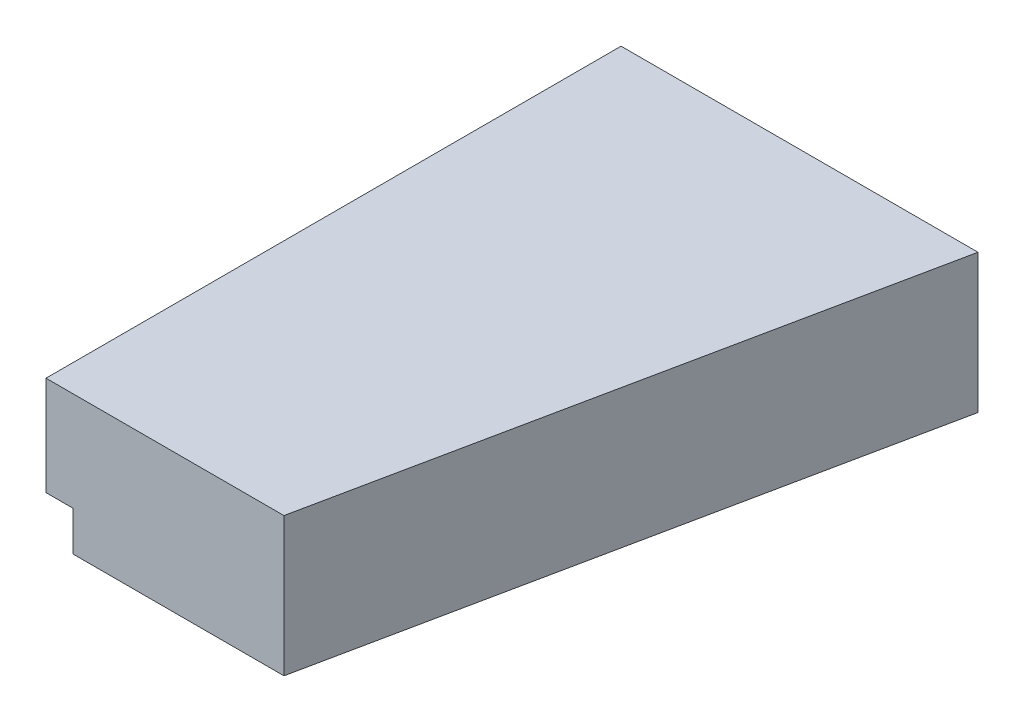
SolidWorks part; units mm, degrees
ref_plane "Front Plane" through (0, 0, 0) normal (1, 0, 0) x (0, 1, 0)
ref_plane "Top Plane" through (0, 0, 0) normal (0, 0, 1) x (0, 1, 0)
ref_plane "Right Plane" through (0, 0, 0) normal (0, 1, 0) x (-1, 0, 0)
sketch "Sketch1" plane through (0, 0, 0) normal (0, 1, 0) x (-1, 0, 0)
  line L0 (-13.4363, 2.5951) -> (16.5637, 147.5951)
  line L1 (-13.4363, -4.9049) -> (-8.4363, -4.9049)
  line L2 (-13.4363, -4.9049) -> (-13.4363, 2.5951)
  line L3 (-13.4363, 2.5951) -> (-8.4363, 2.5951)
  line L4 (-8.4363, -4.9049) -> (-8.4363, 2.5951)
  line L13 (-13.4363, 2.5951) -> (16.5637, 147.5951)
  line L14 (-13.4363, 2.5951) -> (-3.6437, 0.569)
  line L15 (-13.4363, 2.5951) -> (66.5637, 2.5951) construction
  line L16 (-13.4363, 2.5951) -> (-13.4363, 137.5951) construction
  line L17 (-13.4363, 137.5951) -> (66.5637, 137.5951) construction
  line L18 (66.5637, 2.5951) -> (66.5637, 137.5951) construction
  line L19 (66.5637, 137.5951) -> (16.5637, 137.5951)
  line L20 (66.5637, 137.5951) -> (66.5637, 147.5951)
  line L21 (66.5637, 147.5951) -> (16.5637, 147.5951)
  line L22 (16.5637, 137.5951) -> (16.5637, 147.5951)
  line L23 (16.5637, 147.5951) -> (26.3563, 145.569)
  line L24 (-3.6437, 0.569) -> (26.3563, 145.569)
  line L25 (-8.4363, 2.5951) -> (-3.2246, 2.5951)
  line L27 (-3.2246, 2.5951) -> (66.5637, 2.5951)
  line L28 (-3.2246, 2.5951) -> (-3.2246, 7.5951)
  line L29 (-3.2246, 7.5951) -> (66.5637, 7.5951)
  line L30 (66.5637, 2.5951) -> (66.5637, 7.5951)
  line L35 (66.5637, 147.5951) -> (76.5637, 147.5951)
  line L36 (66.5637, 147.5951) -> (66.5637, 2.5951)
  line L37 (66.5637, 2.5951) -> (76.5637, 2.5951)
  line L38 (76.5637, 147.5951) -> (76.5637, 2.5951)
  dimension "D1" = 7.5
  dimension "D3" = 135
  dimension "D4" = 80
  dimension "D5" = 10
  dimension "D7" = 10
  dimension "D9" = 5
  dimension "D8" = 10
  dimension "D6" = 50
extrude "Boss-Extrude1" add sketch "Sketch1" along normal blind 35 contours L24 L19 L20 L21 L23 | L19 L24 L23 L22 | L3 L25 L24 L19 L22 L0 | L29 L28 L24 | L27 L30 L29 L24 | L38 L35 L20 L36 L30 L37 region at (-5.7274, 0, 70.7433) region at (-20.91, 0, 142.2574) region at (-45.5816, 0, 142.6608) region at (-71.5637, 0, 75.0951) region at (2.8797, 0, 5.9284) region at (-31.9275, 0, 5.0889)
sketch "Sketch2" plane through (0, 35, 0) normal (0, 1, 0) x (-1, 0, 0)
  line L0 (16.5637, 147.5951) -> (76.5637, 147.5951)
  line L1 (76.5637, 147.5951) -> (76.5637, 2.5951)
  line L2 (76.5637, 2.5951) -> (-13.4363, 2.5951)
  line L3 (-13.4363, 2.5951) -> (16.5637, 147.5951)
  line L5 (-13.4363, 2.5951) -> (76.5637, 2.5951) construction
extrude "Boss-Extrude2" add sketch "Sketch2" against normal blind 10
sketch "Sketch3" plane through (0, 0, 0) normal (0, -1, 0) x (1, 0, 0)
  line L1 (-24.7065, 147.5951) -> (-66.5637, 147.5951)
  line L2 (-24.7065, 147.5951) -> (-24.7065, 137.5951)
  line L3 (-24.7065, 137.5951) -> (-66.5637, 137.5951)
  line L4 (-66.5637, 147.5951) -> (-66.5637, 137.5951)
  line L8 (13.4363, 2.5951) -> (-76.5637, 2.5951) construction
  line L17 (-76.5637, 147.5951) -> (-16.5637, 147.5951) construction
  line L19 (-24.7065, 137.5951) -> (2.1901, 7.5951) construction
  line L22 (3.2246, 2.5951) -> (-24.7065, 137.5951)
  line L23 (3.2246, 2.5951) -> (13.0172, 4.6211)
  line L24 (-24.7065, 137.5951) -> (-14.9139, 139.6211)
  line L26 (13.0172, 4.6211) -> (-14.9139, 139.6211)
  line L28 (-27.9565, 140.8451) -> (-63.3137, 140.8451)
  line L29 (-63.3137, 144.3451) -> (-63.3137, 140.8451)
  line L30 (-27.9565, 144.3451) -> (-63.3137, 144.3451)
  line L31 (-27.9565, 144.3451) -> (-27.9565, 140.8451)
  line L32 (-20.8654, 135.071) -> (-17.438, 135.7801)
  line L33 (9.1761, 7.1453) -> (-17.438, 135.7801)
  line L34 (5.7487, 6.4361) -> (9.1761, 7.1453)
  line L35 (5.7487, 6.4361) -> (-20.8654, 135.071)
  line L36 (-17.438, 135.7801) -> (-20.8654, 135.071)
  line L37 (-20.8654, 135.071) -> (-23.4566, 147.5951)
  line L38 (-17.438, 135.7801) -> (-19.8825, 147.5951)
  line L39 (-27.9565, 140.8451) -> (-18.4859, 140.8451)
  line L40 (-27.9565, 144.3451) -> (-19.2101, 144.3451)
  line L41 (-19.2101, 144.3451) -> (-18.4859, 140.8451)
  point P5 (-4.1009, 2.5951)
  dimension "D1" = 3.25
extrude "Cut-Extrude1" cut sketch "Sketch3" against normal blind 10 contours L31 L30 L29 L28 | L35 L34 L33 L32 region at (-45.6351, 0, 142.5951) region at (-5.8447, 0, 71.1081)
sketch "Sketch4" plane through (0, 0, 22.5951) normal (0, 1, 0) x (1, 0, 0)
  line L5 (13.4363, 20) -> (-76.5637, 20) construction
  line L6 (-66.5637, 15) -> (2.1901, 15)
  line L7 (-66.5637, 15) -> (-66.5637, 20)
  line L8 (-66.5637, 20) -> (2.1901, 20)
  line L9 (2.1901, 15) -> (2.1901, 20)
  line L10 (2.1901, 15) -> (3.2246, 20)
  line L11 (2.1901, 15) -> (-24.7065, -115) construction
  line L12 (3.2246, 20) -> (2.1901, 20)
  line M13 (2.1901, 15) -> (-66.5637, 15)
  line M20 (-76.5637, 20) -> (13.4363, 20)
extrude "Cut-Extrude2" cut sketch "Sketch4" along normal blind 0.625 contours L9 L7 M13 M20 | L10 L9 M20 region at (-32.1868, 0, 5.0951) region at (2.5349, 0, 4.2617)
sketch "Sketch5" plane through (0, 0, 7.5951) normal (0, 0, 1) x (1, 0, 0)
  line L1 (-66.5637, 0.625) -> (-59.3137, 0.625) construction
  line L2 (-66.5637, 0.625) -> (-66.5637, 5.625) construction
  line L3 (-66.5637, 5.625) -> (-59.3137, 5.625) construction
  line L4 (-59.3137, 0.625) -> (-59.3137, 5.625) construction
  circle A0 centre (-59.3137, 5.625) radius 1.9
  dimension "D3" = 3.8
  dimension "D1" = 5
  dimension "D2" = 7.25
extrude "Cut-Extrude3" cut sketch "Sketch5" against normal up to next contours A0
sketch "Sketch6" plane through (0, 0, 7.5951) normal (0, 0, 1) x (1, 0, 0)
  circle A0 centre (-59.3137, 5.625) radius 3.35
  dimension "D1" = 6.7
extrude "Cut-Extrude4" cut sketch "Sketch6" against normal blind 2.5
pattern_linear "LPattern1" count 2 spacing 52.5 along (1, 0, 0) of "Cut-Extrude4", "Cut-Extrude3"
sketch "Sketch7" plane through (0, 0, 0) normal (0, -1, 0) x (1, 0, 0)
  line L0 (-66.5637, 2.5951) -> (-76.5637, 2.5951) construction
  line L1 (-76.5637, 147.5951) -> (-73.3137, 147.5951)
  line L2 (-76.5637, 147.5951) -> (-76.5637, 2.5951)
  line L3 (-76.5637, 2.5951) -> (-73.3137, 2.5951)
  line L4 (-73.3137, 147.5951) -> (-73.3137, 2.5951) construction
  line L5 (-76.5637, 147.5951) -> (-16.5637, 147.5951) construction
  line L6 (-66.5637, 2.5951) -> (-69.8137, 2.5951)
  line L7 (-66.5637, 2.5951) -> (-66.5637, 147.5951)
  line L8 (-66.5637, 147.5951) -> (-69.8137, 147.5951)
  line L9 (-69.8137, 2.5951) -> (-69.8137, 147.5951) construction
  line L11 (-69.8137, 2.5951) -> (-73.3137, 2.5951)
  line L12 (-69.8137, 2.5951) -> (-69.8137, 147.5951)
  line L13 (-69.8137, 147.5951) -> (-73.3137, 147.5951)
  line L14 (-73.3137, 2.5951) -> (-73.3137, 147.5951)
  line M13 (-76.5637, 2.5951) -> (-66.5637, 2.5951)
  line M20 (-16.5637, 147.5951) -> (-76.5637, 147.5951)
  line M21 (-76.5637, 147.5951) -> (-76.5637, 2.5951)
  dimension "D1" = 3.25
  dimension "D2" = 3.25
extrude "Cut-Extrude5" cut sketch "Sketch7" against normal blind 10 contours L14 L12 M13 M20 | L14 M13 M20 M21 region at (-74.9387, 0, 75.0951) region at (-71.5637, 0, 75.0951)
sketch "Sketch9" plane through (0, 25, 0) normal (0, -1, 0) x (1, 0, 0)
  line L0 (-26.5637, 62.5951) -> (-15.1843, 7.5951)
  line L1 (-66.5637, 7.5951) -> (-26.5637, 7.5951)
  line L2 (-66.5637, 7.5951) -> (-66.5637, 62.5951)
  line L3 (-66.5637, 62.5951) -> (-26.5637, 62.5951)
  line L4 (-26.5637, 7.5951) -> (-26.5637, 62.5951)
  line L5 (-66.5637, 7.5951) -> (2.1901, 7.5951) construction
  line L6 (-26.5637, 7.5951) -> (-15.1843, 7.5951)
  line L7 (-24.7065, 137.5951) -> (2.1901, 7.5951) construction
  line M6 (-66.5637, 137.5951) -> (-66.5637, 7.5951)
  line M7 (-66.5637, 7.5951) -> (2.1901, 7.5951)
  dimension "D1" = 40
  dimension "D2" = 55
extrude "Cut-Extrude6" cut sketch "Sketch9" against normal blind 5 contours L4 L3 M7 M6 | L4 L0 M7 region at (-46.5637, 25, 35.0951) region at (-22.7706, 25, 25.9284)
sketch "Sketch8" plane through (-76.5637, 0, 0) normal (-1, 0, 0) x (0, -1, 0)
  line L1 (-35, 2.5951) -> (-29, 2.5951) construction
  line L2 (-35, 2.5951) -> (-35, 17.5951) construction
  line L3 (-35, 17.5951) -> (-29, 17.5951) construction
  line L4 (-29, 2.5951) -> (-29, 17.5951) construction
  line L5 (-29, 17.5951) -> (-16, 17.5951)
  line L6 (-29, 17.5951) -> (-29, 46.0951)
  line L7 (-29, 46.0951) -> (-16, 46.0951)
  line L8 (-16, 17.5951) -> (-16, 46.0951)
  dimension "D3" = 28.5
  dimension "D4" = 13
extrude "Cut-Extrude7" cut sketch "Sketch8" against normal up to next
sketch "Sketch11" plane through (-66.5637, 0, 0) normal (1, 0, 0) x (0, 1, 0)
  line L0 (14, 48.0951) -> (14, 15.5951)
  line L1 (16, 46.0951) -> (29, 46.0951)
  line L2 (16, 46.0951) -> (16, 17.5951)
  line L3 (16, 17.5951) -> (29, 17.5951)
  line L4 (29, 46.0951) -> (29, 17.5951)
  line L5 (14, 15.5951) -> (31, 15.5951)
  line L6 (31, 48.0951) -> (31, 15.5951)
  line L7 (14, 48.0951) -> (31, 48.0951)
  dimension "D1" = 2
extrude "Cut-Extrude8" cut sketch "Sketch11" against normal blind 7.5
chamfer "Chamfer1" distance 1 distance2 5 1 edges at (-66.5637, 30, 31.8451) first distance on face at (-66.5637, 30.5, 31.8451)
sketch "Sketch12" plane through (-66.5637, 0, 0) normal (1, 0, 0) x (0, 1, 0)
  line L0 (0, 2.5951) -> (0, 147.5951) construction
  line L1 (0, 137.5951) -> (25, 137.5951)
  line L2 (0, 137.5951) -> (0, 123.0951)
  line L3 (0, 123.0951) -> (25, 123.0951)
  line L4 (25, 137.5951) -> (25, 123.0951)
  line L5 (25, 137.5951) -> (0, 137.5951) construction
  line L6 (25, 137.5951) -> (25, 62.5951) construction
  dimension "D1" = 14.5
extrude "Boss-Extrude3" add sketch "Sketch12" along normal blind 2.5
sketch "Sketch13" plane through (-69.8137, 0, 0) normal (-1, 0, 0) x (0, -1, 0)
  line L1 (-10, 147.5951) -> (-5, 147.5951) construction
  line L2 (-10, 147.5951) -> (-10, 130.3451) construction
  line L3 (-10, 130.3451) -> (-5, 130.3451) construction
  line L4 (-5, 147.5951) -> (-5, 130.3451) construction
  circle A0 centre (-5, 130.3451) radius 2.4
  dimension "D3" = 4.8
  dimension "D1" = 17.25
extrude "Cut-Extrude9" cut sketch "Sketch13" against normal blind 3.8
equation "\"whitekey_cutout_length\"= 101.5"
equation "\"key_mount_recess_length\"=50"
equation "\"key_mount_recess_height\"=12.5"
equation "\"key_mount_recess_depth\"=1.5"
equation "\"wall_thickness\"=10"
equation "\"guide_brace_height\"=20"
equation "\"guide_brace_thickness\"=2"
equation "\"dowel_recess_depth\"=10"
equation "\"dowel_recess_offset\"=3.25"
equation "\"dowel_insert_tolerance\"=0.1"
equation "\"base_mount_height\"=40"
equation "\"base_rear_length\"=80"
equation "\"base_front_length\"=111.5"
equation "\"screw_hole_wall_offset\"=7.25"
equation "\"screw_hole_edge_inset\"=\"dowel_recess_depth\"/2"
equation "\"screw_hole_diameter\"=3.8"
equation "\"screw_head_hole_diameter\"=6.7"
equation "\"screw_nut_hole_side_len\"=3.5"
equation "\"screw_nut_recess_offset\"=0.35"
equation "\"screw_head_and_nut_recess_depth\"=2.5"
equation "\"screw_shaft_diameter\"=3.5"
equation "\"switch_board_width\"=30"
equation "\"switch_board_thickness\"=1.6"
equation "\"switch_board_wall_offset\"=11.5"
equation "\"heatset_insert_hole_diameter\"=4.8"
equation "\"heatset_insert_hole_depth\"=3.8"
equation "\"front_rear_panel_width\"=23.75"
equation "\"front_panel_height\"=24"
equation "\"front_rear_panel_recess_depth\"=5"
equation "\"rod_diameter\"=5"
equation "\"rod_head_diameter\"=8"
equation "\"rod_length_adj\"=0.5"
equation "\"rod_insert_length\"=2.8"
equation "\"switch_black_key_mount_height\"=8"
equation "\"switch_white_key_mount_height\"=3"
equation "\"D5@Sketch1\"=\"wall_thickness\""
equation "\"D7@Sketch1\"=\"wall_thickness\""
equation "\"D2@Sketch1\"=\"wall_thickness\"/2"
equation "\"D4@Sketch1\"=\"base_rear_length\""
equation "\"D3@Sketch1\"=\"interface_panel_height\""
equation "\"D1@Sketch1\"=\"wall_thickness\"*0.75"
equation "\"whitekey_spacing\"=1.25"
equation "\"D1@Boss-Extrude1\"=\"side_panel_depth\""
equation "\"D9@Sketch1\"=\"wall_thickness\"/2"
equation "\"D1@Boss-Extrude2\"=\"wall_thickness\""
equation "\"D8@Sketch1\"=\"wall_thickness\""
equation "\"D1@Sketch3\"=\"dowel_recess_offset\""
equation "\"D1@Cut-Extrude1\"=\"dowel_recess_depth\""
equation "\"side_panel_depth\"=35"
equation "\"D1@Sketch5\"=\"screw_hole_edge_inset\""
equation "\"D2@Sketch5\"=\"screw_hole_wall_offset\""
equation "\"D3@Sketch5\"=\"screw_hole_diameter\""
equation "\"D1@Sketch6\"=\"screw_head_hole_diameter\""
equation "\"D1@Cut-Extrude4\"=\"screw_head_and_nut_recess_depth\""
equation "\"D3@LPattern1\"=\"base_rear_length\"-\"screw_hole_wall_offset\"*2-\"wall_thickness\"-3"
equation "\"D1@Sketch7\"=\"dowel_recess_offset\""
equation "\"D2@Sketch7\"=\"dowel_recess_offset\""
equation "\"D1@Cut-Extrude5\"=\"front_rear_panel_recess_depth\"*2"
equation "\"D1@Cut-Extrude2\"=\"whitekey_spacing\"/2"
equation "\"interface_panel_height\"=135"
equation "\"interface_panel_roof_length\"=50"
equation "\"D6@Sketch1\"=\"interface_panel_roof_length\""
equation "\"D1@Sketch8\"=\"wall_thickness\"*1.5"
equation "\"D2@Sketch8\"=\"wall_thickness\"*0.6"
equation "\"D1@Cut-Extrude6\"=\"wall_thickness\"/2"
equation "\"D2@Sketch9\"=\"interface_panel_height\"/3+\"wall_thickness\""
equation "\"D1@Sketch9\"=\"base_rear_length\"/2"
equation "\"D1@Cut-Extrude8\"=\"wall_thickness\"*0.75"
equation "\"D1@Sketch12\"=\"screw_hole_wall_offset\"*2"
equation "\"D1@Boss-Extrude3\"=\"wall_thickness\"/4"
equation "\"D1@Sketch13\"=\"wall_thickness\"+\"screw_hole_wall_offset\""
equation "\"D2@Sketch13\"=\"screw_hole_edge_inset\""
equation "\"D3@Sketch13\"=\"heatset_insert_hole_diameter\""
equation "\"D1@Cut-Extrude9\"=\"heatset_insert_hole_depth\""
